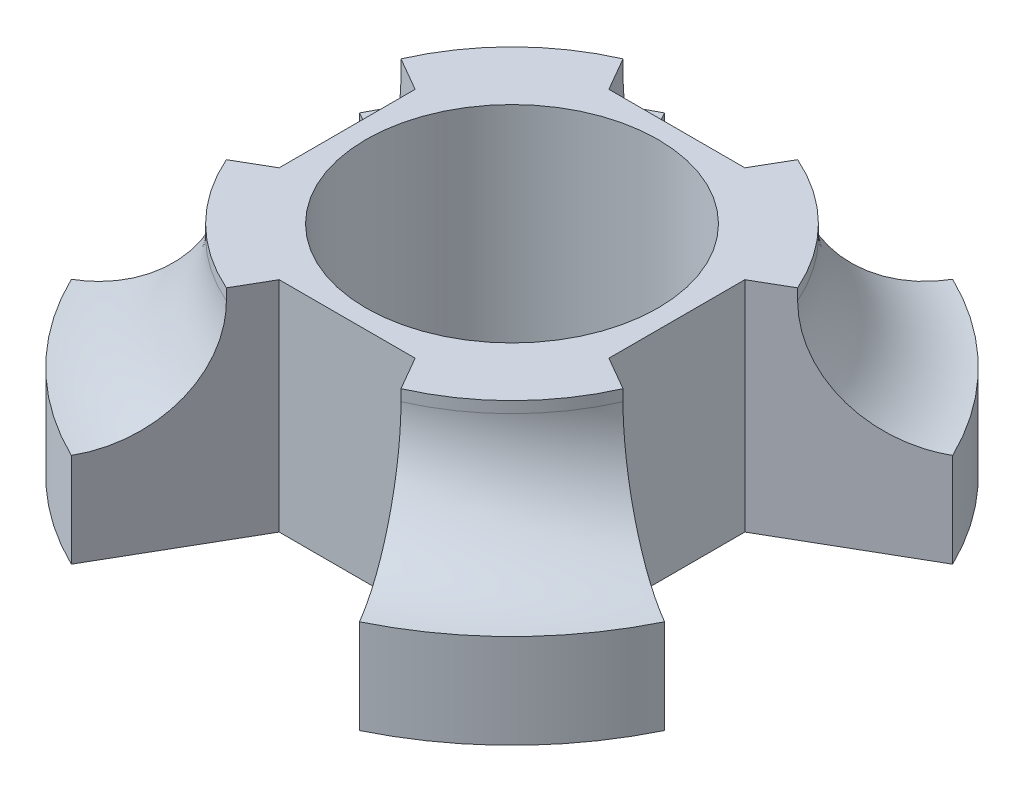
SolidWorks part; units mm, degrees
ref_plane "Alzado" through (0, 0, 0) normal (0, 0, 1) x (1, 0, 0)
ref_plane "Planta" through (0, 0, 0) normal (0, 1, 0) x (1, 0, 0)
ref_plane "Vista lateral" through (0, 0, 0) normal (1, 0, 0) x (0, 0, -1)
sketch "Sketch1" plane through (0, 0, 0) normal (0, 1, 0) x (1, 0, 0)
  circle A0 centre (0, 0) radius 11.5
  circle A1 centre (0, 0) radius 7.75
  dimension "D1" = 23
  dimension "D2" = 15.5
extrude "Boss-Extrude1" add sketch "Sketch1" along normal blind 11.4
sketch "Sketch2" plane through (0, 11.4, 0) normal (0, 1, 0) x (1, 0, 0)
  circle A0 centre (0, 0) radius 7.75
  circle A1 centre (0, 0) radius 11.5
  circle A2 centre (0, 0) radius 7.75 construction
  dimension "D1" = 23
extrude "Boss-Extrude2" add sketch "Sketch2" along normal blind 0.2
sketch "Sketch5" plane through (0, 0, 0) normal (0, 1, 0) x (1, 0, 0)
  circle A0 centre (0, 0) radius 17.5
  circle A1 centre (0, 0) radius 7.75 construction
  circle A2 centre (0, 0) radius 7.75
  dimension "D1" = 35
extrude "Boss-Extrude3" add sketch "Sketch5" along normal blind 5
fillet "Fillet1" radius 6 1 edges at (0, 5, 11.5) type face fillet first side face at (0, 0, 7.75) first side face at (0, 5, 11.5) second side face at (0, 5, 17.5)
sketch "Sketch6" plane through (0, 11.6, 0) normal (0, 1, 0) x (1, 0, 0)
  line L0 (-11.5, 0) -> (11.5, 0) construction
  line L1 (7.2169, 15) -> (3.6084, 21.25) construction
  line L2 (3.6084, 21.25) -> (-3.6084, 21.25)
  line L3 (-3.6084, 21.25) -> (-7.2169, 15) construction
  line L4 (-7.2169, 15) -> (-3.6084, 8.75)
  line L5 (-3.6084, 8.75) -> (3.6084, 8.75)
  line L6 (3.6084, 8.75) -> (7.2169, 15)
  line L7 (-7.2169, 15) -> (-7.6451, 15.7417)
  line L8 (-7.6451, 15.7417) -> (-3.6084, 21.25)
  line L9 (7.2169, 15) -> (7.6451, 15.7417)
  line L10 (7.6451, 15.7417) -> (3.6084, 21.25)
  circle A0 centre (0, 15) radius 6.25 construction
  circle A2 centre (0, 0) radius 11.5 construction
  circle A3 centre (0, 0) radius 17.5 construction
  point P18 (0, 0)
  dimension "D1" = 15
  dimension "D2" = 12.5
extrude "Cut-Extrude2" cut sketch "Sketch6" against normal through all
pattern_circular "CirPattern1" count 4 over 360 about axis through (0, 11.4, 0) along (0, -1, 0) of "Cut-Extrude2"
